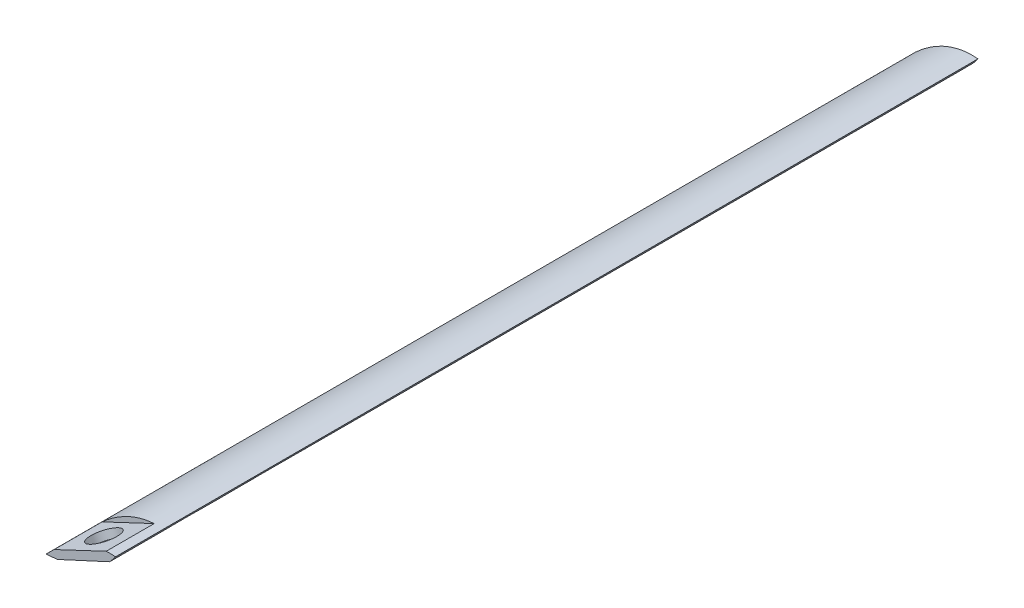
SolidWorks part; units mm, degrees
ref_plane "前视基准面" through (0, 0, 0) normal (0, 0, 1) x (1, 0, 0)
ref_plane "上视基准面" through (0, 0, 0) normal (0, 1, 0) x (1, 0, 0)
ref_plane "右视基准面" through (0, 0, 0) normal (1, 0, 0) x (0, 0, -1)
sketch "草图1" plane through (0, 0, 0) normal (0, 0, 1) x (1, 0, 0)
  line L0 (0, 0) -> (7.2503, 3.3813) construction
  spline S0 degree 3 poles (0, 0) (1.8222, 1.9631) (4.4469, 3.6581) (7.2503, 3.3813) knots 0 0 0 0 1 1 1 1
  spline S1 degree 3 poles (0, 0) (2.6751, 0.1343) (5.6605, 1.0557) (7.2503, 3.3813) knots 0 0 0 0 1 1 1 1
extrude "凸台-拉伸1" add sketch "草图1" along normal blind 90
ref_axis "基准轴1" through (7.2503, 3.3813, 90) along (-0.9063, -0.4227, 0)
ref_plane "基准面4" through (0, 0, 0) normal (-0.4227, 0.9063, 0) x (-0.9063, -0.4227, 0)
sketch "草图3" plane through (0, 0, 0) normal (-0.4227, 0.9063, 0) x (-0.9063, -0.4227, 0)
  line L0 (0, 90) -> (-8, 90) construction
  line L1 (0, 90) -> (-8, 90) construction
  line L2 (-4, 90.1113) -> (-4, 85.8941) construction
  circle A0 centre (-4, 87.4065) radius 1.5
  point P3 (-4, 90)
extrude "切除-拉伸1" cut sketch "草图3" against normal through all and the other way through all
sketch "草图4" plane through (0, 0, 90) normal (0, 0, 1) x (1, 0, 0)
  line L0 (6.2839, 3.4007) -> (0.8477, 0.8376)
  line L1 (0.8477, 0.8376) -> (-0.2041, 3.0683)
  line L2 (-0.2041, 3.0683) -> (5.3753, 5.699)
  line L3 (5.3753, 5.699) -> (6.2839, 3.4007)
  spline S0 degree 3 poles (7.2503, 3.3813) (4.4469, 3.6581) (1.8222, 1.9631) (0, 0) knots 0 0 0 0 1 1 1 1 construction
extrude "切除-拉伸2" cut sketch "草图4" against normal blind 5
mirror "镜向1" about plane through (0, 0, 0) normal (-0.4227, 0.9063, 0) of "切除-拉伸2"
